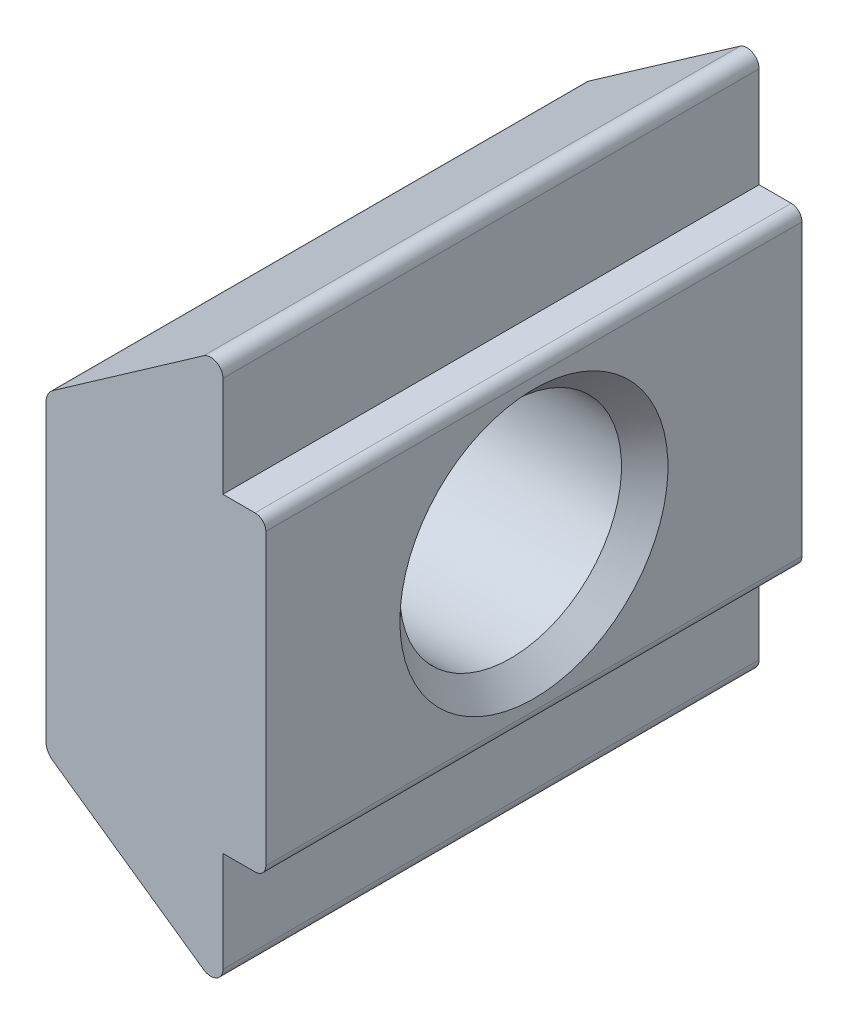
SolidWorks part; units mm, degrees
material "Alloy Steel"
ref_plane "Front Plane" through (0, 0, 0) normal (0, 0, 1) x (1, 0, 0)
ref_plane "Top Plane" through (0, 0, 0) normal (0, 1, 0) x (1, 0, 0)
ref_plane "Right Plane" through (0, 0, 0) normal (1, 0, 0) x (0, 0, -1)
ref_plane "Plane1" through (0, 0, 0) normal (0, 0, 1) x (1, 0, 0)
sketch "Sketch1" plane through (0, 0, 0) normal (0, 0, 1) x (1, 0, 0)
  line L0 (-3.972, -2.9896) -> (-1.1589, -4.9588)
  line L1 (-0.8, -4.7719) -> (-0.8, -2.9)
  line L2 (-0.8, -2.9) -> (-0.2, -2.9)
  line L3 (0, -2.7) -> (0, 2.7)
  line L4 (-0.2, 2.9) -> (-0.8, 2.9)
  line L5 (-0.8, 2.9) -> (-0.8, 4.7719)
  line L6 (-1.1589, 4.9588) -> (-3.972, 2.9896)
  line L7 (-4.1, 2.7438) -> (-4.1, -2.7438)
  arc A0 (-4.1, -2.7438) -> (-3.972, -2.9896) centre (-3.8, -2.7438) ccw
  arc A1 (-1.1589, -4.9588) -> (-0.8, -4.7719) centre (-1.0281, -4.7719) ccw
  arc A2 (-0.2, -2.9) -> (0, -2.7) centre (-0.2, -2.7) ccw
  arc A3 (0, 2.7) -> (-0.2, 2.9) centre (-0.2, 2.7) ccw
  arc A4 (-0.8, 4.7719) -> (-1.1589, 4.9588) centre (-1.0281, 4.7719) ccw
  arc A5 (-3.972, 2.9896) -> (-4.1, 2.7438) centre (-3.8, 2.7438) ccw
extrude "Boss-Extrude1" add sketch "Sketch1" against normal blind 5 and the other way blind 5
ref_plane "Plane2" through (0, 0, 0) normal (0, 0, 1) x (1, 0, 0)
sketch "Sketch2" plane through (0, 0, 0) normal (0, 0, 1) x (1, 0, 0)
  line L0 (-4.1, 0) -> (-4.1, 2.5)
  line L1 (-4.1, 2.5) -> (-3.667, 2.067)
  line L2 (-3.667, 2.067) -> (-0.433, 2.067)
  line L3 (-0.433, 2.067) -> (0, 2.5)
  line L4 (0, 2.5) -> (0, 0)
  line L5 (0, 0) -> (-4.1, 0)
  line L6 (0, 0) -> (-4.1, 0) construction
revolve "Cut-Revolve1" cut sketch "Sketch2" angle 360 about L6 reverse direction yes
